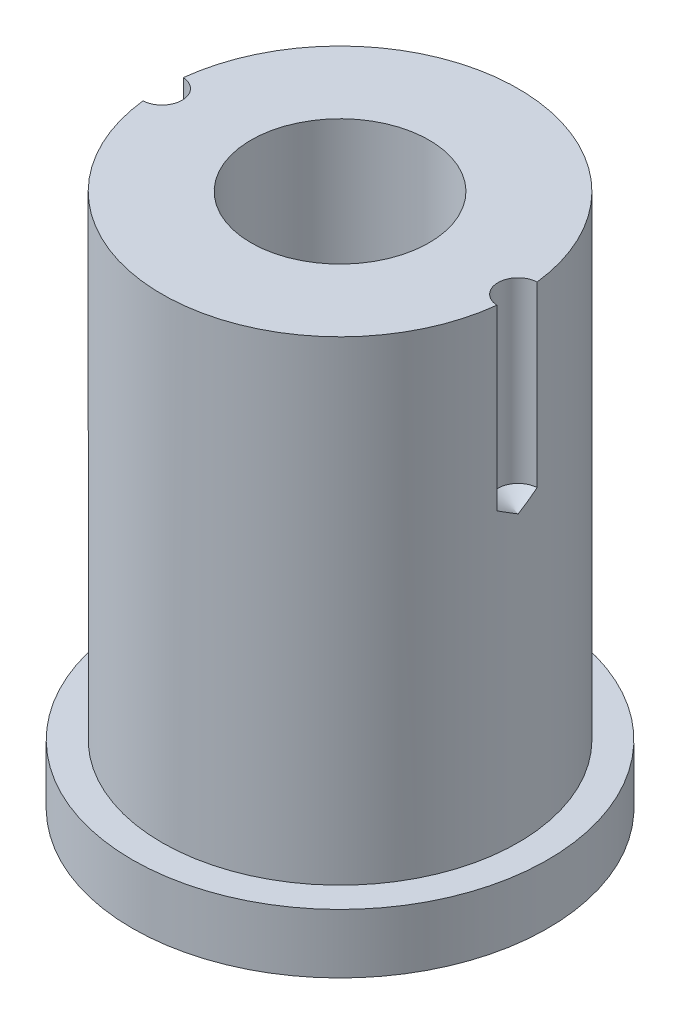
SolidWorks part; units mm, degrees
material "Commercial Bronze, UNS C22000 (90-10 Bronze)"
ref_plane "Front Plane" through (0, 0, 0) normal (0, 0, 1) x (1, 0, 0)
ref_plane "Top Plane" through (0, 0, 0) normal (0, 1, 0) x (1, 0, 0)
ref_plane "Right Plane" through (0, 0, 0) normal (1, 0, 0) x (0, 0, -1)
sketch "Sketch4" plane through (0, 0, 0) normal (0, 1, 0) x (1, 0, 0)
  circle A0 centre (0, 0) radius 35
  dimension "D1" = 70
extrude "Boss-Extrude2" add sketch "Sketch4" along normal blind 10
sketch "Sketch5" plane through (0, 10, 0) normal (0, 1, 0) x (1, 0, 0)
  circle A0 centre (0, 0) radius 30
  dimension "D1" = 60
extrude "Boss-Extrude3" add sketch "Sketch5" along normal blind 80
sketch "Sketch6" plane through (0, 90, 0) normal (0, 1, 0) x (1, 0, 0)
  circle A0 centre (0, 0) radius 15
  dimension "D1" = 30
extrude "Cut-Extrude1" cut sketch "Sketch6" against normal up to next
hole_wizard "M8 Tapped Hole2" positions "Sketch7" profile "Sketch8" tap size "M8" standard "ISO"
sketch "Sketch7" plane through (0, 90, 0) normal (0, 1, 0) x (1, 0, 0)
  circle A0 centre (0, 0) radius 30 construction
  circle A1 centre (0, 0) radius 30 construction
  point P0 (-30, 0)
  point P4 (30, 0)
sketch "Sketch8" plane through (-30, 90, 0) normal (1, 0, 0) x (0, 0, 1)
  line L0 (0, 0) -> (0, 32.0429)
  line L1 (0, 32.0429) -> (3.4, 30)
  line L2 (3.4, 30) -> (3.4, 0)
  line L5 (3.4, 0) -> (0, 0)
  line L10 (0, 32.0429) -> (-3.4, 30) construction
  line L11 (0, -6.35) -> (0, 107.95) construction
  dimension "Tap Drill Dia." = 6.8
  dimension "Tap Drill Depth" = 30
  dimension "Drill Angle" = 118
